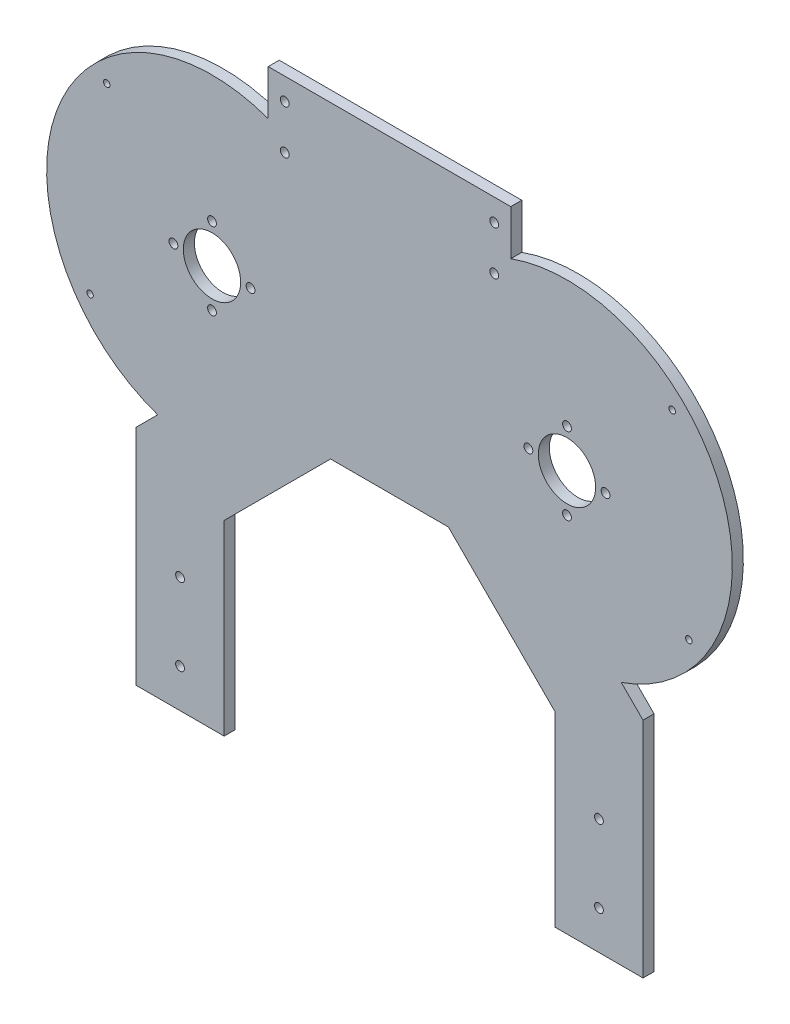
SolidWorks part; units mm, degrees
ref_plane "Front Plane" through (0, 0, 0) normal (0, 0, 1) x (1, 0, 0)
ref_plane "Top Plane" through (0, 0, 0) normal (0, 1, 0) x (1, 0, 0)
ref_plane "Right Plane" through (0, 0, 0) normal (1, 0, 0) x (0, 0, -1)
sketch "Sketch1" plane through (0, 0, 0) normal (0, 0, 1) x (1, 0, 0)
  line L1 (-100, -75) -> (100, -75)
  line L2 (-100, -75) -> (-100, 75)
  line L3 (-100, 75) -> (100, 75)
  line L4 (100, -75) -> (100, 75)
  line L5 (-100, -75) -> (100, 75) construction
  line L6 (-100, 75) -> (100, -75) construction
  line L8 (-47.5, 40) -> (47.5, 40) construction
  line L9 (0, 75) -> (0, -75) construction
  line L10 (-27, -44) -> (27, -44) construction
  line L11 (-27, -44) -> (-27, 28) construction
  line L12 (-27, 28) -> (27, 28) construction
  line L13 (27, -44) -> (27, 28) construction
  line L14 (-27, -44) -> (27, 28) construction
  line L15 (-27, 28) -> (27, -44) construction
  line L23 (-55, 70) -> (55, 70)
  line L24 (-55, 70) -> (-55, -70)
  line L25 (-55, -70) -> (55, -70)
  line L26 (55, 70) -> (55, -70)
  line L27 (-55, 70) -> (55, -70) construction
  line L28 (-55, -70) -> (55, 70) construction
  line L29 (-32.5, 70) -> (32.5, 70) construction
  line L30 (-32.5, 70) -> (-32.5, 55) construction
  line L31 (-32.5, 55) -> (32.5, 55) construction
  line L32 (32.5, 70) -> (32.5, 55) construction
  line L33 (-32.5, 70) -> (32.5, 55) construction
  line L34 (-32.5, 55) -> (32.5, 70) construction
  circle A2 centre (-47.5, 40) radius 2
  circle A3 centre (47.5, 40) radius 2
  circle A4 centre (-27, 28) radius 2 construction
  circle A5 centre (27, 28) radius 2 construction
  circle A6 centre (27, -44) radius 2 construction
  circle A7 centre (-27, -44) radius 2 construction
  circle A8 centre (-47.5, 60) radius 2
  circle A10 centre (47.5, 60) radius 2
  point P0 (0, 0)
  point P15 (0, 40)
  point P18 (0, -8)
  point P56 (0, 0)
  point P63 (0, 62.5)
  dimension "D3" = 4
  dimension "D4" = 20
  dimension "D5" = 4
  dimension "D8" = 4
  dimension "D1" = 150
  dimension "D2" = 200
  dimension "D6" = 72
  dimension "D7" = 54
  dimension "D14" = 30
  dimension "D15" = 140
  dimension "D16" = 110
  dimension "D17" = 95
  dimension "D18" = 12
  dimension "D19" = 15
  dimension "D20" = 65
extrude "Boss-Extrude1" add sketch "Sketch1" along normal blind 5 contours L23 L32 L31 L30 L24 L25 L26 A7 A6 A5 A4 A3 A2 region at (0, -0.1637, 0)
sketch "Sketch2" plane through (0, 0, 0) normal (0, 0, 1) x (1, 0, 0)
  line L0 (-55, -70) -> (-100.8579, -115.8579) construction
  line L1 (-55, 70) -> (-55, -70) construction
  line L2 (-55, -41.7157) -> (-115, -101.7157)
  line L3 (-26.7157, -70) -> (-86.7157, -130)
  line L4 (-55, -70) -> (55, -70) construction
  line L5 (-115, -101.7157) -> (-86.7157, -130)
  line L6 (-115, -101.7157) -> (-115, -203)
  line L7 (-75, -118.2843) -> (-75, -203)
  line L8 (-75, -203) -> (-115, -203)
  line L9 (0, 75) -> (0, -75) construction
  line L10 (-55, -41.7157) -> (-26.7157, -70)
  line L11 (-55, 70) -> (-55, -70) construction
  line L12 (-115, -203) -> (-75, -203) construction
  circle A0 centre (-95, -150.5) radius 2
  circle A1 centre (-95, -185.5) radius 2
  circle A2 centre (-95, -150.5) radius 2 construction
  circle A4 centre (-95, -185.5) radius 2 construction
  dimension "D1" = 135
  dimension "D2" = 40
  dimension "D3" = 40
  dimension "D4" = 75
  dimension "D5" = 0
extrude "Boss-Extrude2" add sketch "Sketch2" along normal blind 5 contours L8 L7 L3 L5 L6 | L10 L2 L5 L3 region at (-70.8579, -85.8579, 0) region at (-95.9289, -160.2024, 0)
mirror "Mirror1" about plane through (0, 0, 0) normal (1, 0, 0) of "Boss-Extrude2"
sketch "Sketch3" plane through (0, 0, 5) normal (0, 0, 1) x (1, 0, 0)
  line L0 (0, 31.3301) -> (0, 52.1198) construction
  line L1 (-80.5, -21) -> (-128.2297, 26.7297) construction
  line L2 (-80.5, -21) -> (80.5, -21) construction
  line L3 (-80.5, -21) -> (-148, -21) construction
  line L4 (-80.5, -21) -> (-135.7928, -59.7164) construction
  circle A0 centre (-80.5, -21) radius 75
  circle A1 centre (-80.5, -3.5) radius 2
  circle A2 centre (80.5, -21) radius 75
  circle A3 centre (-80.5, -21) radius 60
  circle A4 centre (80.5, -21) radius 60
  circle A5 centre (-47.5, 40) radius 2 construction
  circle A6 centre (-47.5, 40) radius 2
  circle A7 centre (47.5, 40) radius 2
  circle A8 centre (-63, -21) radius 2
  circle A9 centre (-80.5, -38.5) radius 2
  circle A10 centre (-98, -21) radius 2
  circle A11 centre (98, -21) radius 2
  circle A12 centre (80.5, -38.5) radius 2
  circle A13 centre (63, -21) radius 2
  circle A14 centre (80.5, -3.5) radius 2
  circle A15 centre (-80.5, -21) radius 13
  circle A16 centre (80.5, -21) radius 13
  circle A17 centre (-128.2297, 26.7297) radius 1.4732
  circle A18 centre (-135.7928, -59.7164) radius 1.4732
  circle A19 centre (-80.5, -21) radius 67.5 construction
  circle A20 centre (128.2297, 26.7297) radius 1.4732
  circle A21 centre (135.7928, -59.7164) radius 1.4732
  point P28 (-80.5, -21)
  line M3 (115, -101.7157) -> (55, -41.7157)
  line M4 (55, -41.7157) -> (55, 70)
  line M6 (-55, 70) -> (-55, -41.7157)
  line M7 (-55, -41.7157) -> (-115, -101.7157)
  line M11 (-75, -118.2843) -> (-26.7157, -70)
  line M12 (-26.7157, -70) -> (26.7157, -70)
  line M13 (26.7157, -70) -> (75, -118.2843)
  circle M17 centre (-47.5, 40) radius 2
  circle M18 centre (47.5, 40) radius 2
  dimension "D1" = 161
  dimension "D2" = 150
  dimension "D3" = 61
  dimension "D4" = 120
  dimension "D5" = 4
  dimension "D7" = 35
  dimension "D8" = 26
  dimension "D9" = 7.5
  dimension "D10" = 2.9464
  dimension "D6" = 4
  dimension "D11" = 45
  dimension "D12" = 35
extrude "Boss-Extrude3" add sketch "Sketch3" against normal up to surface (5 mm away) contours A3 M6 M7 | A3 A0 M6 M7 | A3 A0 M7 M11 M12 M6 M17 | A3 M7 M6 | A4 M3 M4 | A4 M4 M3 | A4 A2 M4 M3 | A4 A2 M3 M4 M12 M13 M18 region at (-11.8554, -46.5242, 5) region at (9.6495, -2.4591, 5) region at (-56.7712, 41.4218, 5) region at (-96.2806, -16.4848, 5) region at (-46.5969, -30.7004, 5) region at (122.5668, 38.9404, 5) region at (46.5969, -30.7004, 5) region at (96.2806, -16.4848, 5) up to face at (0, -95.388, 0)
